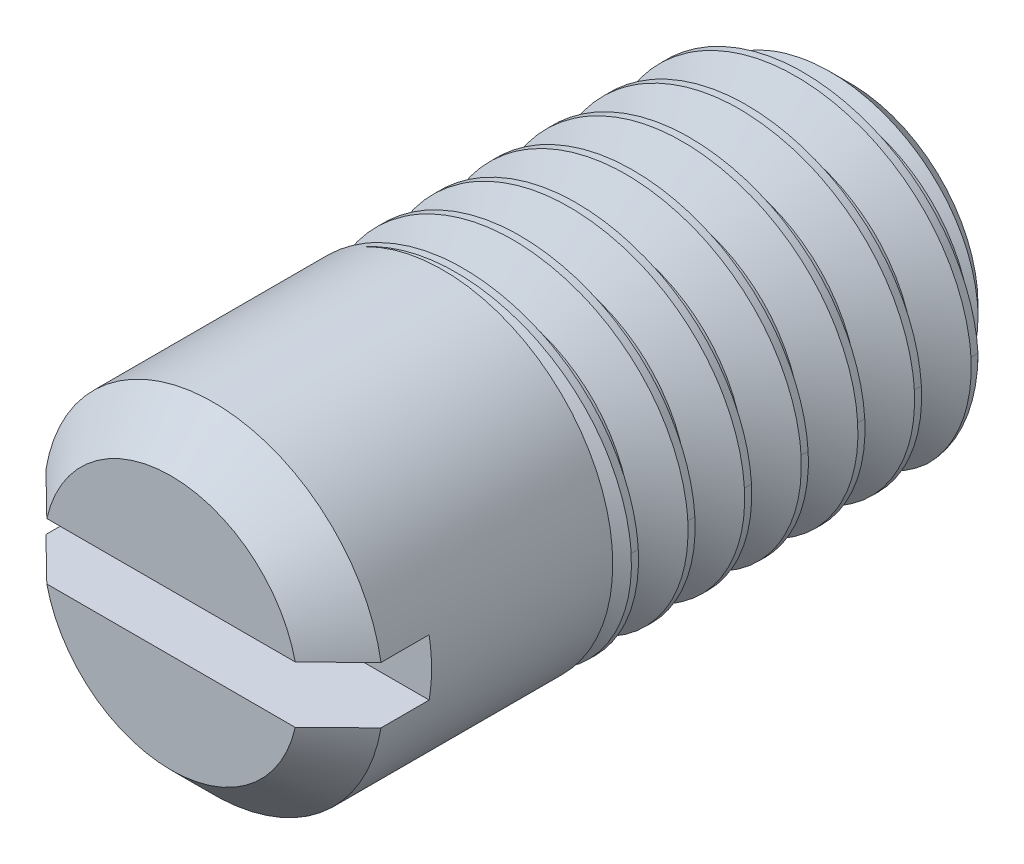
SolidWorks part; units mm, degrees
ref_plane "Front Plane" through (0, 0, 0) normal (0, 0, 1) x (1, 0, 0)
ref_plane "Top Plane" through (0, 0, 0) normal (0, 1, 0) x (1, 0, 0)
ref_plane "Right Plane" through (0, 0, 0) normal (1, 0, 0) x (0, 0, -1)
sketch "Sketch1" plane through (0, 0, 0) normal (1, 0, 0) x (0, 0, -1)
  line L0 (-2.4, 0) -> (3.6, 0) construction
  line L1 (3.6, 1.5) -> (3.6, -1.5) construction
  line L2 (-2.4, 0.25) -> (-2.4, -0.25) construction
  line L3 (-2.4, -0.25) -> (-1.6, -0.25) construction
  line L4 (3.6, 1.5) -> (3.1, 1.5) construction
  line L5 (3.1, 1.5) -> (0, 1.5) construction
  line L6 (0, 1.5) -> (-2.4, 1.5) construction
  point P5 (3.6, 0)
  point P9 (0, 0)
  dimension "Oall Length" = 6
  dimension "Thread Diameter" = 3
  dimension "Thread Length" = 3.6
  dimension "Slot Width n" = 0.5
  dimension "Slot Depth t" = 0.8
  dimension "Pitch" = 0.5
sketch "Sketch2" plane through (0, 0, 0) normal (1, 0, 0) x (0, 0, -1)
  line L0 (3.6, 0) -> (3.6, 1.5)
  line L1 (3.6, 1.5) -> (-2.4, 1.5)
  line L2 (-2.4, 1.5) -> (-2.4, 0)
  line L3 (-2.4, 0) -> (3.6, 0)
revolve "Revolve1" add sketch "Sketch2" angle 360 about L0
fillet "Chamfer2" radius 0.375 2 edges at (1.5, 0, 2.4) (1.5, 0, -3.6) profile chamfer
sketch "Sketch3" plane through (0, 0, 0) normal (1, 0, 0) x (0, 0, -1)
  line L0 (-1.6, -0.25) -> (-2.4, -0.25)
  line L1 (-2.4, -0.25) -> (-2.4, 0.25)
  line L2 (-2.4, 0.25) -> (-1.6, 0.25)
  line L3 (-1.6, 0.25) -> (-1.6, -0.25)
extrude "Cut-Extrude1" cut sketch "Sketch3" against normal through all both and the other way through all
sketch "Sketch4" plane through (0, 0, -3.6) normal (0, 0, -1) x (-1, 0, 0)
  circle A0 centre (0, 0) radius 1.5
curve "Helix/Spiral1" pitch 0.5 height 4.1 radius 1.5 centre (0, 0, -3.6) axis (0, 0, 1) start towards (0, 1, 0) parameters "pitch"=0.5
sketch "Sketch5" plane through (0, 0, 0) normal (1, 0, 0) x (0, 0, -1)
  line L0 (3.6, 1.5) -> (4.0375, 1.5) construction
  line L1 (4.0375, 1.5) -> (3.8187, 1.1211) construction
  line L2 (3.8187, 1.1211) -> (3.6, 1.5) construction
  line L3 (3.7875, 1.1752) -> (3.85, 1.1752) construction
  line L4 (3.8187, 1.1752) -> (3.8187, 1.5) construction
  line L5 (3.6937, 1.3376) -> (3.9437, 1.3376) construction
  line L6 (3.6, 1.5) -> (4.0375, 1.5)
  line L7 (4.0375, 1.5) -> (3.85, 1.1752)
  line L8 (3.85, 1.1752) -> (3.7875, 1.1752)
  line L9 (3.7875, 1.1752) -> (3.6, 1.5)
  point P7 (3.8187, 1.3376)
  dimension "D1" = 0.0625
  dimension "D2" = 0.25
sweep "Cut-Sweep1" cut profiles "Sketch5" path "Helix/Spiral1" align with end faces yes
sketch "Sketch6" plane through (0, 0, 0) normal (0, 0, 1) x (1, 0, 0)
  circle A1 centre (0, 0) radius 1.5
  circle A2 centre (0, 0) radius 1.5
  dimension "D1" = 0
extrude "Boss-Extrude2" add sketch "Sketch6" along normal blind 0.5
ref_axis "Center Axis 1" through (0, 0, -3.2302) along (0, 0, 1)
ref_plane "Contact Plane 1" through (0, 0, 0) normal (0, 0, 1) x (1, 0, 0)
equation "\"3..6250in\"=4.625"
equation "\"Slot Width n@Sketch1\"=\"Pitch@Sketch1\""
equation "\"Slot Depth t@Sketch1\"=\"Pitch@Sketch1\"*1.6"
equation "\"D1@Chamfer2\"=\"Pitch@Sketch1\"*.75"
equation "\"D1@Sketch5\"=\"Pitch@Sketch1\"*.125"
equation "\"D2@Sketch5\"=\"Pitch@Sketch1\"*.5"
equation "\"D3@Helix/Spiral1\"=\"Thread Length@Sketch1\"+(\"Pitch@Sketch1\")"
equation "\"D1@Boss-Extrude2\"=\"Pitch@Sketch1\""
